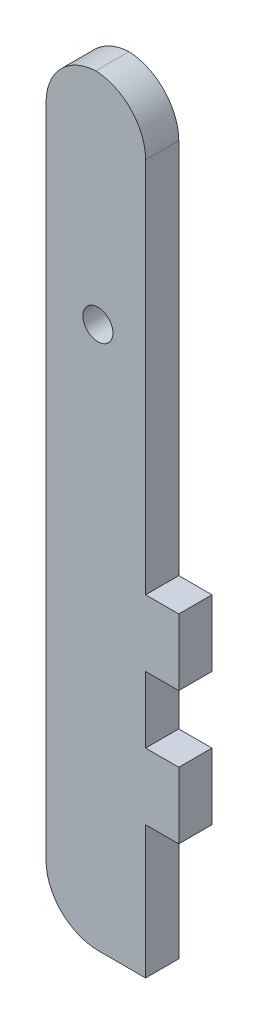
SolidWorks part; units mm, degrees
ref_plane "Front Plane" through (0, 0, 0) normal (0, 0, 1) x (1, 0, 0)
ref_plane "Top Plane" through (0, 0, 0) normal (0, 1, 0) x (1, 0, 0)
ref_plane "Right Plane" through (0, 0, 0) normal (1, 0, 0) x (0, 0, -1)
sketch "Sketch1" plane through (0, 0, 0) normal (0, 0, 1) x (1, 0, 0)
  line L0 (-44.45, 19.05) -> (-44.45, 101.1289)
  line L1 (-44.45, -44.45) -> (-63.5, -44.45)
  line L2 (-44.45, -44.45) -> (-44.45, -19.05)
  line L3 (-44.45, 101.1289) -> (-63.5, 101.1289)
  line L4 (-63.5, -44.45) -> (-63.5, 101.1289)
  line L5 (-44.45, 19.05) -> (-38.1, 19.05)
  line L6 (-44.45, -6.35) -> (-44.45, 6.35)
  line L7 (-44.45, 6.35) -> (-38.1, 6.35)
  line L8 (-38.1, 19.05) -> (-38.1, 6.35)
  line L9 (-44.45, -6.35) -> (-38.1, -6.35)
  line L11 (-44.45, -19.05) -> (-38.1, -19.05)
  line L12 (-38.1, -6.35) -> (-38.1, -19.05)
  dimension "D1" = 19.05
extrude "Boss-Extrude1" add sketch "Sketch1" along normal blind 6.35
fillet "Fillet1" radius 10 3 edges at (-63.5, -44.45, 3.175) (-44.45, 101.1289, 3.175) (-63.5, 101.1289, 3.175)
sketch "Sketch2" plane through (0, 0, 0) normal (0, 0, -1) x (-1, 0, 0)
  circle A0 centre (53.575, 59.2899) radius 2.8702
extrude "Cut-Extrude3" cut sketch "Sketch2" against normal through all
